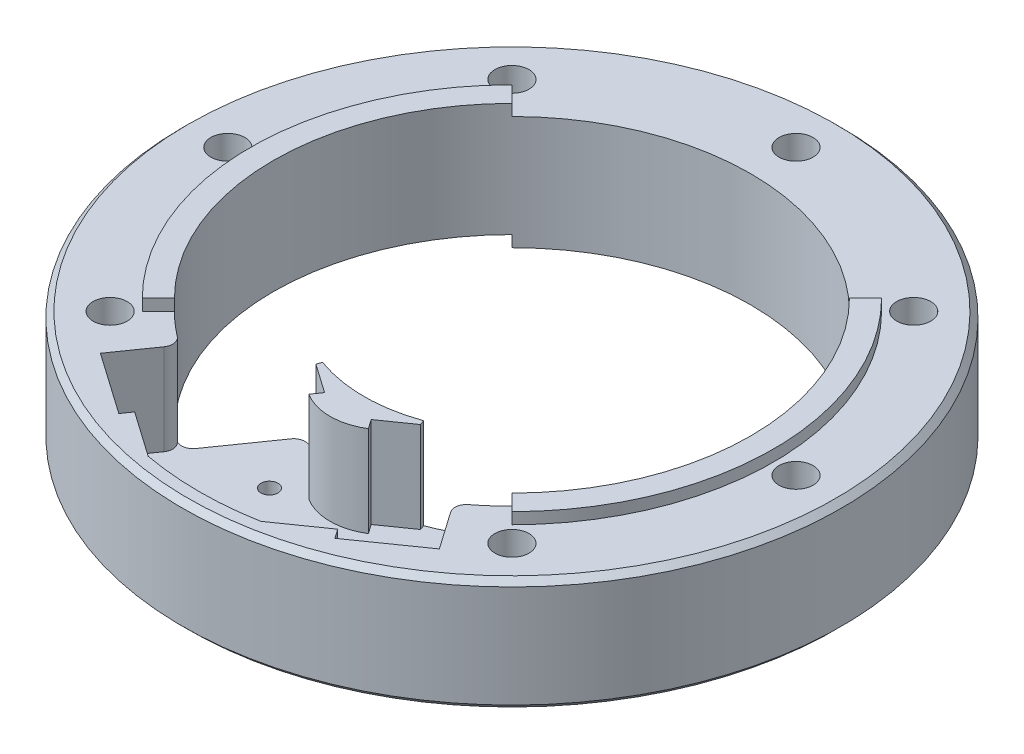
SolidWorks part; units mm, degrees
material "ABS"
ref_plane "Front" through (0, 0, 0) normal (0, 0, 1) x (1, 0, 0)
ref_plane "Top" through (0, 0, 0) normal (0, 1, 0) x (1, 0, 0)
ref_plane "Right" through (0, 0, 0) normal (1, 0, 0) x (0, 0, -1)
sketch "Szkic1" plane through (0, 0, 0) normal (0, 0, 1) x (1, 0, 0)
  line L0 (0, 10) -> (0, 0) construction
  line L1 (29, 9.5) -> (29, 0.5)
  line L4 (23, 0) -> (28.5, 0)
  line L5 (21, 11) -> (21, 10)
  line L6 (23, 10) -> (28.5, 10)
  line L7 (13, 10) -> (13, 0)
  line L10 (28.5, 10) -> (29, 9.5)
  line L11 (29, 0.5) -> (28.5, 0)
  line L20 (23, 11) -> (23, 10)
  line L21 (21, 11) -> (23, 11)
  line L22 (20, 1) -> (23, 1)
  line L23 (23, 1) -> (23, 0)
  line L24 (20, 1) -> (20, 0)
  line L25 (13, 10) -> (21, 10)
  line L26 (13, 0) -> (20, 0)
  dimension "D1" = 10
revolve "Obrót1" add sketch "Szkic1" angle 360 about L0
sketch "Szkic3" plane through (0, 10, 0) normal (0, 1, 0) x (1, 0, 0)
  line L0 (-11.4572, -16.3625) -> (-8.0096, -11.4388)
  line L1 (0, 0) -> (0, -35.3956) construction
  line L2 (11.4572, -16.3625) -> (8.0096, -11.4388)
  arc A0 (12.8901, -16.5784) -> (11.4572, -16.3625) centre (12.2763, -15.789) cw
  arc A1 (8.0096, -11.4388) -> (6.6768, -11.1544) centre (7.1904, -12.0124) ccw
  arc A2 (-6.6768, -11.1544) -> (-8.0096, -11.4388) centre (-7.1904, -12.0124) ccw
  arc A3 (-11.4572, -16.3625) -> (-12.8901, -16.5784) centre (-12.2763, -15.789) cw
  arc A6 (12.8901, -16.5784) -> (-12.8901, -16.5784) centre (0, 0) ccw
  arc A10 (-6.6768, -11.1544) -> (6.6768, -11.1544) centre (0, 0) ccw
  circle A11 centre (8.9818, -21.5445) radius 0.75
  circle A12 centre (-5.1962, -16.1381) radius 0.75
  circle A13 centre (5.1962, -16.1381) radius 0.75
  circle A14 centre (-8.9818, -21.5445) radius 0.75
  point P8 (12.0451, -17.2022)
  point P15 (-12.0451, -17.2022)
  dimension "D1" = 21
  dimension "D2" = 1
  dimension "D3" = 1.5
  dimension "D4" = 1.5
  dimension "D5" = 1.5
  dimension "D6" = 1.5
extrude "Wytnij-wyciągnięcie1" cut sketch "Szkic3" against normal through all
sketch "Szkic4" plane through (0, 10, 0) normal (0, 1, 0) x (1, 0, 0)
  line L173 (8.933, -24.2644) -> (4.9548, -27.0499)
  line L174 (-8.933, -24.2644) -> (-4.9548, -27.0499)
  line L175 (-9.5066, -25.0836) -> (-8.933, -24.2644)
  line L176 (-14.913, -21.298) -> (-9.5066, -25.0836)
  line L177 (-7.4565, -10.649) -> (-14.913, -21.298)
  line L178 (-4.6031, -12.6469) -> (-2.0501, -14.4346)
  line L179 (-2.0501, -14.4346) -> (-2.6237, -15.2537)
  line L180 (-4.4463, -12.216) -> (-4.6031, -12.6469)
  line L181 (4.6031, -12.6469) -> (2.0501, -14.4346)
  line L182 (2.0501, -14.4346) -> (2.6237, -15.2537)
  line L183 (4.4463, -12.216) -> (4.6031, -12.6469)
  line L184 (14.913, -21.298) -> (9.5066, -25.0836)
  line L185 (9.5066, -25.0836) -> (8.933, -24.2644)
  line L186 (7.4565, -10.649) -> (14.913, -21.298)
  arc A0 (4.4463, -12.216) -> (7.4565, -10.649) centre (0, 0) ccw
  arc A9 (-4.9548, -27.0499) -> (4.9548, -27.0499) centre (0, 0) ccw
  arc A10 (-7.4565, -10.649) -> (-4.4463, -12.216) centre (0, 0) ccw
  arc A15 (-2.6237, -15.2537) -> (2.6237, -15.2537) centre (0, -11.0641) ccw
extrude "Wytnij-wyciągnięcie2" cut sketch "Szkic4" against normal blind 8
sketch "Szkic5" plane through (0, 10, 0) normal (0, 1, 0) x (1, 0, 0)
  line L0 (0, 0) -> (0, 45.3272) construction
  line L1 (-16.2635, -16.2635) -> (-14.8492, -14.8492)
  line L2 (16.2635, -16.2635) -> (14.8492, -14.8492)
  line L3 (-14.8492, 14.8492) -> (-16.2635, 16.2635)
  line L4 (14.8492, 14.8492) -> (16.2635, 16.2635)
  arc A0 (16.2635, 16.2635) -> (0, 23) centre (0, 0) ccw
  arc A1 (14.8492, 14.8492) -> (0, 21) centre (0, 0) ccw
  arc A2 (0, 21) -> (-14.8492, 14.8492) centre (0, 0) ccw
  arc A3 (0, 23) -> (-16.2635, 16.2635) centre (0, 0) ccw
  arc A4 (-16.2635, -16.2635) -> (16.2635, -16.2635) centre (0, 0) ccw
  arc A5 (-14.8492, -14.8492) -> (14.8492, -14.8492) centre (0, 0) ccw
  dimension "D1" = 45
extrude "Wytnij-wyciągnięcie3" cut sketch "Szkic5" along normal blind 8
sketch "Szkic6" plane through (0, 0, 0) normal (0, -1, 0) x (1, 0, 0)
  line L0 (0, 0) -> (0, -32.1579) construction
  line L1 (16.2635, 16.2635) -> (14.8492, 14.8492)
  line L2 (-16.2635, 16.2635) -> (-14.8492, 14.8492)
  line L3 (-14.8492, -14.8492) -> (-16.2635, -16.2635)
  line L4 (14.8492, -14.8492) -> (16.2635, -16.2635)
  arc A0 (-16.2635, -16.2635) -> (16.2635, -16.2635) centre (0, 0) ccw
  arc A1 (-14.8492, -14.8492) -> (14.8492, -14.8492) centre (0, 0) ccw
  arc A2 (14.8492, 14.8492) -> (12.8901, 16.5784) centre (0, 0) ccw
  arc A3 (16.2635, 16.2635) -> (-16.2635, 16.2635) centre (0, 0) ccw
  arc A4 (11.4718, 16.3829) -> (-11.4718, 16.3829) centre (0, 0) ccw
  arc A5 (-12.8901, 16.5784) -> (-14.8492, 14.8492) centre (0, 0) ccw
  arc A6 (12.8901, 16.5784) -> (11.4718, 16.3829) centre (12.2763, 15.789) ccw
  arc A7 (-11.4718, 16.3829) -> (-12.8901, 16.5784) centre (-12.2763, 15.789) ccw
  point P23 (-12.0451, 17.2022)
  dimension "D2" = 1
  dimension "D1" = 45
extrude "Dodanie-wyciągnięcie1" add sketch "Szkic6" against normal blind 1
sketch "Szkic7" plane through (0, 10, 0) normal (0, 1, 0) x (1, 0, 0)
  circle A0 centre (0, 25) radius 1.5
  dimension "D1" = 3
  dimension "D2" = 25
extrude "Wytnij-wyciągnięcie4" cut sketch "Szkic7" against normal through all
pattern_circular "Szyk kołowy1" count 8 over 360 about axis through (0, 10, 0) along (0, 1, 0) of "Wytnij-wyciągnięcie4"
fillet "Zaokrąglenie1" radius 1 2 edges at (-11.4572, 6, 16.3625) (11.4572, 6, 16.3625)
